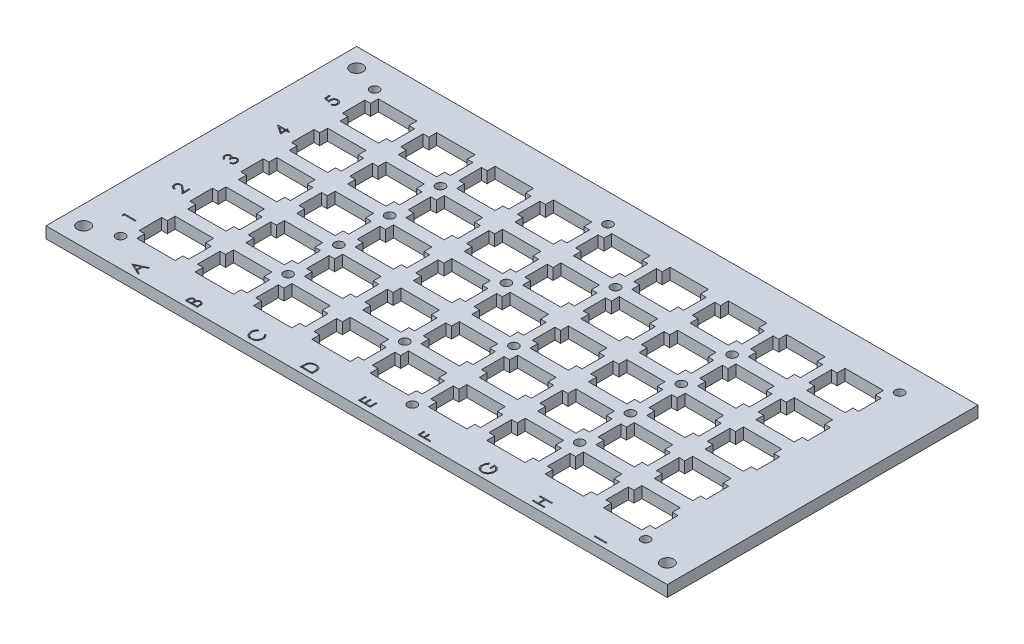
SolidWorks part; units mm, degrees
ref_plane "Front Plane" through (0, 0, 0) normal (0, 0, 1) x (1, 0, 0)
ref_plane "Top Plane" through (0, 0, 0) normal (0, 1, 0) x (1, 0, 0)
ref_plane "Right Plane" through (0, 0, 0) normal (1, 0, 0) x (0, 0, -1)
sketch "Sketch1" plane through (0, 0, 0) normal (0, 1, 0) x (1, 0, 0)
  line L1 (-1.3921, 0.4858) -> (193.7079, 0.4858)
  line L2 (-1.3921, 0.4858) -> (-1.3921, -112.0642)
  line L3 (-1.3921, -112.0642) -> (193.7079, -112.0642)
  line L4 (193.7079, 0.4858) -> (193.7079, -112.0642)
  dimension "D1" = 195.1
  dimension "D2" = 112.55
extrude "Boss-Extrude1" add sketch "Sketch1" along normal blind 8
sketch "Sketch2" plane through (0, 8, 0) normal (0, 1, 0) x (1, 0, 0)
  line L1 (15.7579, -13.8642) -> (25.9579, -13.8642)
  line L2 (15.7579, -13.8642) -> (15.7579, -24.0642)
  line L3 (15.7579, -24.0642) -> (25.9579, -24.0642)
  line L4 (25.9579, -13.8642) -> (25.9579, -24.0642)
  line L5 (-1.3921, 0.4858) -> (-1.3921, -112.0642) construction
  line L6 (15.7579, -15.9642) -> (14.2579, -15.9642)
  line L7 (15.7579, -15.9642) -> (15.7579, -21.9642)
  line L8 (15.7579, -21.9642) -> (14.2579, -21.9642)
  line L9 (14.2579, -15.9642) -> (14.2579, -21.9642)
  line L10 (25.9579, -15.9642) -> (27.4579, -15.9642)
  line L11 (25.9579, -15.9642) -> (25.9579, -21.9642)
  line L12 (25.9579, -21.9642) -> (27.4579, -21.9642)
  line L13 (27.4579, -15.9642) -> (27.4579, -21.9642)
  line L14 (193.7079, 0.4858) -> (-1.3921, 0.4858) construction
  point P16 (14.2579, -18.9642)
  point P17 (15.7579, -18.9642)
  dimension "D1" = 10.2
  dimension "D2" = 10.2
  dimension "D4" = 1.5
  dimension "D7" = 1.5
  dimension "D3" = 15.65
  dimension "D8" = 14.35
  dimension "D9" = 0
  dimension "D10" = 0
  dimension "D5" = 6
  dimension "D6" = 0
extrude "Cut-Extrude1" cut sketch "Sketch2" against normal offset from surface (3 mm away) 3 contours L4 L1 L2 L3 | L13 L10 L4 L12 | L6 L9 L8 L2 region at (20.8579, 8, 18.9642) region at (15.0079, 8, 18.9642) region at (26.7079, 8, 18.9642) up to face at (96.1579, 8, 55.7892)
sketch "Sketch3" plane through (0, 5, 0) normal (0, 1, 0) x (1, 0, 0)
  line L0 (15.7579, -13.8642) -> (25.9579, -13.8642) construction
  line L1 (27.4579, -21.9642) -> (27.4579, -15.9642) construction
  circle A0 centre (21.3579, -18.9642) radius 1.25
  point P4 (20.8579, -13.8642)
  point P7 (27.4579, -18.9642)
  dimension "D1" = 2.5
  dimension "D2" = 0.5
  dimension "D3" = 0
extrude "Cut-Extrude2" cut sketch "Sketch3" against normal through all
pattern_linear "LPattern1" count 9 spacing 15.5 along (1, 0, 0) count 5 spacing 13.5 along (0, 0, 1) of "Cut-Extrude1", "Cut-Extrude2"
sketch "Sketch5" plane through (0, 8, 0) normal (0, 1, 0) x (1, 0, 0)
  line L1 (165.9079, -4.6892) -> (0.8079, -4.6892)
  line L2 (165.9079, -4.6892) -> (165.9079, -87.2392)
  line L3 (165.9079, -87.2392) -> (0.8079, -87.2392)
  line L4 (0.8079, -4.6892) -> (0.8079, -87.2392)
  line L5 (165.9079, -4.6892) -> (0.8079, -87.2392) construction
  line L6 (165.9079, -87.2392) -> (0.8079, -4.6892) construction
  line L7 (-1.3921, 0.4858) -> (193.7079, 0.4858)
  line L8 (-1.3921, 0.4858) -> (-1.3921, -112.0642)
  line L9 (-1.3921, -112.0642) -> (193.7079, -112.0642)
  line L10 (193.7079, 0.4858) -> (193.7079, -112.0642)
  point P0 (83.3579, -45.9642)
  dimension "D1" = 165.1
  dimension "D2" = 82.55
extrude "Cut-Extrude4" cut sketch "Sketch5" against normal through all both and the other way through all
sketch "Sketch6" plane through (0, 8, 0) normal (0, 1, 0) x (1, 0, 0)
  line L0 (0.8079, -4.6892) -> (0.8079, -87.2392) construction
  line L1 (0.8079, -87.2392) -> (165.9079, -87.2392) construction
  line L2 (165.9079, -4.6892) -> (0.8079, -4.6892) construction
  line L3 (165.9079, -87.2392) -> (165.9079, -4.6892) construction
  point P0 (5.8079, -82.2392)
  point P6 (5.8079, -9.6892)
  point P8 (160.9079, -82.2392)
  dimension "D1" = 5
  dimension "D2" = 5
  dimension "D3" = 5
  dimension "D4" = 5
  dimension "D5" = 5
  dimension "D6" = 5
hole_wizard "1/8 (0.133) Dowel Hole1" positions "Sketch7" profile "Sketch8" hole size "1/8" standard "ANSI Inch" end condition through all
sketch "Sketch7" plane through (0, 8, 0) normal (0, 1, 0) x (1, 0, 0)
  point P0 (5.8079, -9.6892)
  point P3 (5.8079, -82.2392)
  point P6 (160.9079, -82.2392)
sketch "Sketch8" plane through (5.8079, 8, 9.6892) normal (1, 0, 0) x (0, 0, 1)
  line L0 (0, 0) -> (0, 8)
  line L1 (0, 8) -> (1.6891, 8)
  line L2 (1.6891, 8) -> (1.6891, 0)
  line L5 (1.6891, 0) -> (0, 0)
  line L11 (0, -6.35) -> (0, 107.95) construction
  dimension "Thru Hole Dia." = 3.3782
  dimension "Thru Hole Depth" = 8
sketch "Sketch9" plane through (0, 8, 0) normal (0, 1, 0) x (1, 0, 0)
  line L1 (0.8079, -87.2392) -> (165.9079, -87.2392)
  line L2 (0.8079, -87.2392) -> (0.8079, -4.6892)
  line L3 (0.8079, -4.6892) -> (165.9079, -4.6892)
  line L4 (165.9079, -87.2392) -> (165.9079, -4.6892)
extrude "Cut-Extrude6" [suppressed] cut sketch "Sketch9" along normal through all from surface
sketch "Sketch10" plane through (0, 8, 0) normal (0, 1, 0) x (1, 0, 0)
  line L1 (15.7579, -78.0642) -> (25.9579, -78.0642) construction
  line L2 (16.6079, -77.5642) -> (16.6079, -79.7142) construction
  point P0 (13.1079, -79.7142)
  point P5 (16.6079, -78.6392)
  point P9 (28.6079, -79.7142)
  point P10 (44.1079, -79.7142)
  point P11 (59.6079, -79.7142)
  point P12 (75.1079, -79.7142)
  point P13 (90.6079, -79.7142)
  point P14 (106.1079, -79.7142)
  point P15 (121.6079, -79.7142)
  point P16 (137.1079, -79.7142)
  point P17 (152.6079, -79.7142)
  point P18 (28.6079, -66.2142)
  point P19 (44.1079, -66.2142)
  point P20 (59.6079, -66.2142)
  point P21 (75.1079, -66.2142)
  point P22 (90.6079, -66.2142)
  point P23 (106.1079, -66.2142)
  point P24 (121.6079, -66.2142)
  point P25 (137.1079, -66.2142)
  point P26 (152.6079, -66.2142)
  point P27 (28.6079, -52.7142)
  point P28 (44.1079, -52.7142)
  point P29 (59.6079, -52.7142)
  point P30 (75.1079, -52.7142)
  point P31 (90.6079, -52.7142)
  point P32 (106.1079, -52.7142)
  point P33 (121.6079, -52.7142)
  point P34 (137.1079, -52.7142)
  point P35 (152.6079, -52.7142)
  point P36 (28.6079, -39.2142)
  point P37 (44.1079, -39.2142)
  point P38 (59.6079, -39.2142)
  point P39 (75.1079, -39.2142)
  point P40 (90.6079, -39.2142)
  point P41 (106.1079, -39.2142)
  point P42 (121.6079, -39.2142)
  point P43 (137.1079, -39.2142)
  point P44 (152.6079, -39.2142)
  point P45 (28.6079, -25.7142)
  point P46 (44.1079, -25.7142)
  point P47 (59.6079, -25.7142)
  point P48 (75.1079, -25.7142)
  point P49 (90.6079, -25.7142)
  point P50 (106.1079, -25.7142)
  point P51 (121.6079, -25.7142)
  point P52 (137.1079, -25.7142)
  point P53 (152.6079, -25.7142)
  point P54 (28.6079, -12.2142)
  point P55 (44.1079, -12.2142)
  point P56 (59.6079, -12.2142)
  point P57 (75.1079, -12.2142)
  point P58 (90.6079, -12.2142)
  point P59 (106.1079, -12.2142)
  point P60 (121.6079, -12.2142)
  point P61 (137.1079, -12.2142)
  point P62 (152.6079, -12.2142)
  point P63 (13.1079, -66.2142)
  point P64 (13.1079, -52.7142)
  point P65 (13.1079, -39.2142)
  point P66 (13.1079, -25.7142)
  point P67 (13.1079, -12.2142)
  dimension "D1" = 1.65
  dimension "D2" = 3.5
  dimension "D3" = 10
  dimension "D4" = 6
hole_wizard "M2 Clearance Hole1" positions "Sketch13" profile "Sketch12" hole size "M2" standard "ANSI Metric" end condition through all
sketch "Sketch13" plane through (0, 8, 0) normal (0, 1, 0) x (1, 0, 0)
  point P0 (13.1079, -79.7142)
  point P3 (13.1079, -12.2142)
  point P6 (44.1079, -66.2142)
  point P9 (44.1079, -52.7142)
  point P12 (44.1079, -39.2142)
  point P15 (44.1079, -25.7142)
  point P18 (152.6079, -79.7142)
  point P21 (152.6079, -12.2142)
  point P24 (121.6079, -66.2142)
  point P27 (121.6079, -52.7142)
  point P30 (121.6079, -39.2142)
  point P33 (121.6079, -25.7142)
  point P36 (90.6079, -25.7142)
  point P39 (75.1079, -39.2142)
  point P42 (90.6079, -52.7142)
  point P45 (75.1079, -66.2142)
  point P48 (90.6079, -79.7142)
  point P51 (75.1079, -12.2142)
sketch "Sketch12" plane through (13.1079, 8, 79.7142) normal (1, 0, 0) x (0, 0, 1)
  line L0 (0, 0) -> (0, 8)
  line L1 (0, 8) -> (1.2, 8)
  line L2 (1.2, 8) -> (1.2, 0)
  line L5 (1.2, 0) -> (0, 0)
  line L11 (0, -6.35) -> (0, 107.95) construction
  dimension "Thru Hole Dia." = 2.4
  dimension "Thru Hole Depth" = 8
pattern_sketch "Sketch-Pattern1" [suppressed] of bodies 113 driven by "Sketch10"
sketch "Sketch14" plane through (0, 8, 0) normal (0, 1, 0) x (1, 0, 0)
  text T0 "1         2         3         4         5\r\n"
  text T1 "<r90>A          B           C         D          E           F           G         H           I</r>"
extrude "Cut-Extrude7" cut sketch "Sketch14" against normal blind 0.8
sketch "Sketch15" plane through (0, 5, 0) normal (0, 1, 0) x (1, 0, 0)
  line L1 (0.8079, -87.2392) -> (165.9079, -87.2392)
  line L2 (0.8079, -87.2392) -> (0.8079, -4.6892)
  line L3 (0.8079, -4.6892) -> (165.9079, -4.6892)
  line L4 (165.9079, -87.2392) -> (165.9079, -4.6892)
extrude "Cut-Extrude8" cut sketch "Sketch15" against normal blind 10
equation "\"length\"= 6.5 * 25.4"
equation "\"width\"= ( 6.5 * 25.4 ) / 2"
equation "\"border\" = 3"
equation "\"slidelength\"= 10"
equation "\"slidewidth\"= 10"
equation "\"griptol\" = 1.5"
equation "\"slidetol\"= 0.1"
equation "\"D2@Sketch2\"= \"slidelength\" + 2*(\"slidetol\")"
equation "\"D1@Sketch2\"= \"slidewidth\" + 2 * \"slidetol\""
equation "\"D4@Sketch2\"= \"griptol\""
equation "\"D7@Sketch2\"= \"griptol\""
equation "\"D3@LPattern1\"= 15.5"
equation "\"D4@LPattern1\" = 13.5"
equation "\"D2@Sketch1\"=\"width\"+30"
equation "\"D1@Sketch1\"=\"length\"+30"
